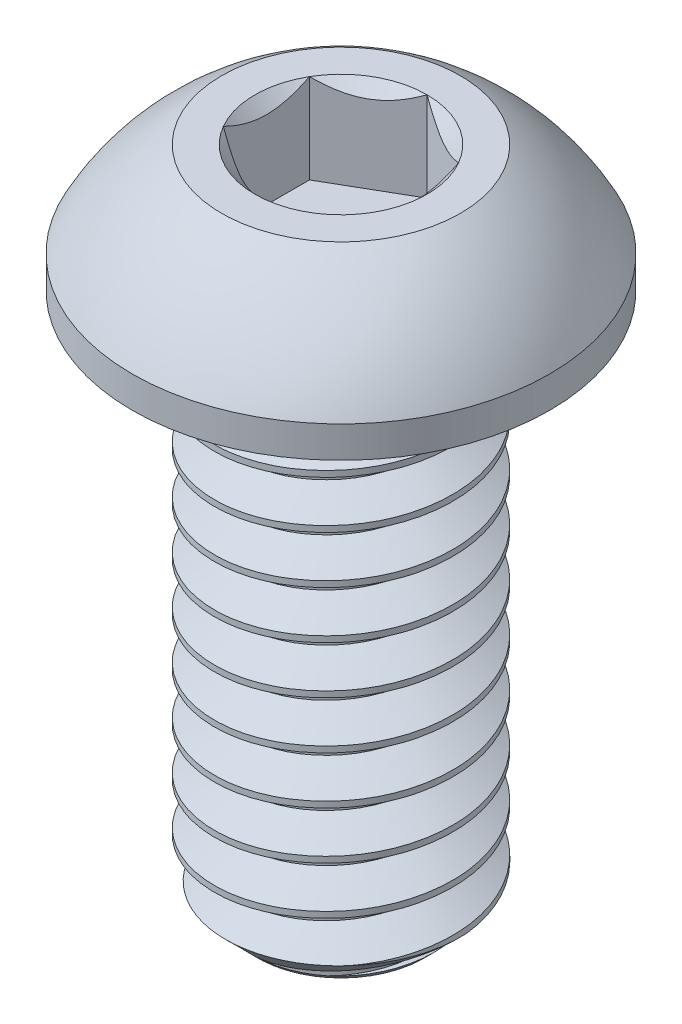
SolidWorks part; units mm, degrees
ref_plane "Front Plane" through (0, 0, 0) normal (0, 0, 1) x (1, 0, 0)
ref_plane "Top Plane" through (0, 0, 0) normal (0, 1, 0) x (1, 0, 0)
ref_plane "Right Plane" through (0, 0, 0) normal (1, 0, 0) x (0, 0, -1)
sketch "Sketch1" plane through (0, 0, 0) normal (0, 1, 0) x (1, 0, 0)
  circle A0 centre (0, 0) radius 3.175
  point P2 (3.175, 0)
  point P3 (-3.175, 0)
  dimension "D1" = 6.35
extrude "Boss-Extrude1" add sketch "Sketch1" against normal blind 14.2875
sketch "Sketch2" plane through (0, -14.2875, 0) normal (0, -1, 0) x (1, 0, 0)
  circle A1 centre (0, 0) radius 3.175
  circle A2 centre (0, 0) radius 3.175
  point P0 (0, -3.175)
  dimension "D1" = 0
curve "Helix/Spiral1" pitch 1.27 height 15.5575 turns 12.25
sketch "Sketch3" plane through (0, 0, 0) normal (1, 0, 0) x (0, 0, -1)
  line L0 (3.3125, -14.2081) -> (2.2126, -14.8431) construction
  line L1 (2.2126, -14.8431) -> (3.3125, -15.4781) construction
  line L2 (3.3125, -15.4781) -> (3.3125, -14.2081) construction
  line L3 (2.3501, -14.7637) -> (2.3501, -14.9225) construction
  line L4 (3.175, -14.2875) -> (3.175, -15.3987) construction
  line L5 (2.2126, -14.8431) -> (2.3501, -14.8431) construction
  line L6 (3.175, -14.8431) -> (3.3125, -14.8431) construction
  line L8 (2.2126, -14.8431) -> (-3.175, -14.8431) construction
  line L9 (2.3501, -14.7637) -> (3.2437, -14.2478)
  line L10 (2.3501, -14.7637) -> (2.3501, -14.9225)
  line L11 (2.3501, -14.9225) -> (3.2437, -15.4384)
  line L12 (3.2437, -15.4384) -> (3.2437, -14.2478)
  line L14 (-3.175, -14.8431) -> (-3.175, -13.5731) construction
  line L15 (-3.175, -13.5731) -> (-3.175, -12.3031) construction
  line L16 (-3.175, -12.3031) -> (-3.175, -11.0331) construction
  line L17 (-3.175, -11.0331) -> (-3.175, -9.7631) construction
  line L18 (-3.175, 0) -> (-3.175, -14.2875) construction
  point P15 (3.2437, -14.8431)
  dimension "D1" = 1.27
  dimension "D2" = 0.1588
sweep "Cut-Sweep1" cut profiles "Sketch3" path "Helix/Spiral1" align with end faces yes
sketch "SketchZ" plane through (0, 0, 0) normal (0, 0, 1) x (1, 0, 0)
  line L0 (0, -14.8431) -> (0, -14.2081) construction
  line L1 (0, -14.5256) -> (3.175, -14.5256) construction
  line L2 (3.175, -14.5256) -> (3.175, -13.2556) construction
  line L3 (0, -14.8431) -> (0, -13.5731) construction
sketch "Sketch4" plane through (0, -14.2875, 0) normal (0, -1, 0) x (1, 0, 0)
  circle A0 centre (0, 0) radius 2.2126
extrude "Cut-Extrude1" cut sketch "Sketch4" against normal blind 1.27 draft 45 flip side to cut
sketch "Sketch5" plane through (0, 0, 0) normal (0, 0, 1) x (1, 0, 0)
  line L0 (0, 3.3528) -> (0, 0)
  line L1 (0, 0) -> (-7.112, 0) construction
  line L2 (0, 3.3528) -> (-3.175, 3.3528)
  line L3 (-7.112, 0) -> (-7.112, 0.8382) construction
  line L4 (-7.112, 0.8382) -> (-5.5499, 0.8382) construction
  line L5 (0, 0) -> (0, -13.9857) construction
  line L6 (-5.5499, 0.8382) -> (-5.5499, 0)
  line L7 (-5.5499, 0) -> (0, 0)
  arc A0 (-5.5499, 0.8382) -> (-3.175, 3.3528) centre (0, -2.0246) cw
  dimension "D1" = 11.0998
  dimension "D2" = 7.112
  dimension "D3" = 3.3528
  dimension "D4" = 0.8382
revolve "Revolve1" add sketch "Sketch5" angle 360 mid plane about L5
sketch "Sketch6" plane through (0, 3.3528, 0) normal (0, 1, 0) x (1, 0, 0)
  line L1 (0, 2.2914) -> (-1.9844, 1.1457)
  line L2 (-1.9844, 1.1457) -> (-1.9844, -1.1457)
  line L3 (-1.9844, -1.1457) -> (0, -2.2914)
  line L4 (0, -2.2914) -> (1.9844, -1.1457)
  line L5 (1.9844, -1.1457) -> (1.9844, 1.1457)
  line L6 (1.9844, 1.1457) -> (0, 2.2914)
  circle A0 centre (0, 0) radius 1.9844 construction
extrude "Cut-Extrude2" cut sketch "Sketch6" against normal blind 2.3813
sketch "Sketch7" plane through (0, 3.3528, 0) normal (0, 1, 0) x (1, 0, 0)
  circle A0 centre (0, 0) radius 2.2914
extrude "Cut-Extrude3" cut sketch "Sketch7" against normal blind 2.3813 draft 45
sketch "Sketch8" plane through (0, 0, 0) normal (0, 0, 1) x (1, 0, 0)
  line L0 (5.075, -6.35) -> (5.075, -11.3707) construction
  line L4 (5.075, -11.3707) -> (-5.075, -11.3707) construction
  line L7 (-5.075, -6.35) -> (5.075, -6.35) construction
  line L10 (0, 0) -> (0, -6.35) construction
  line L11 (-5.075, -11.3707) -> (-5.075, -6.35) construction
  line L12 (-5.0233, -6.7522) -> (-2.3801, -10.197)
  line L13 (-4.825, -6.35) -> (4.825, -6.35)
  line L14 (5.0233, -6.7522) -> (2.3801, -10.197)
  line L18 (0, -6.35) -> (0, -11.3707) construction
  arc A1 (-2.3801, -10.197) -> (2.3801, -10.197) centre (0, -8.3707) ccw
  arc A2 (-4.825, -6.35) -> (-5.0233, -6.7522) centre (-4.825, -6.6) ccw
  arc A3 (4.825, -6.35) -> (5.0233, -6.7522) centre (4.825, -6.6) cw
  dimension "D1" = 10.15
  dimension "D3" = 75
  dimension "D4" = 3
  dimension "D6" = 0.25
  dimension "D2" = 6.35
  dimension "D5" = 5.0207
sketch "Sketch9" plane through (0, 0, 0) normal (0, 1, 0) x (1, 0, 0)
  circle A2 centre (0, 0) radius 3.175
  circle A3 centre (0, 0) radius 3.175
  dimension "D2" = 0
equation "\"D3@Helix/Spiral1\" = \"D4@Helix/Spiral1\" + \"D1@Boss-Extrude1\""
equation "\"D1@Sketch3\" = \"D4@Helix/Spiral1\""
equation "\"D2@Sketch3\" = \"D1@Sketch3\" / 8"
equation "\"D1@Cut-Extrude1\" = \"D4@Helix/Spiral1\""
equation "\"D1@Cut-Extrude2\" = \"D1@Sketch6\" * 3/5"
equation "\"D1@Cut-Extrude3\" = \"D1@Cut-Extrude2\""
equation "\"D4@Sketch5\" = \"D3@Sketch5\" * 1/4"
